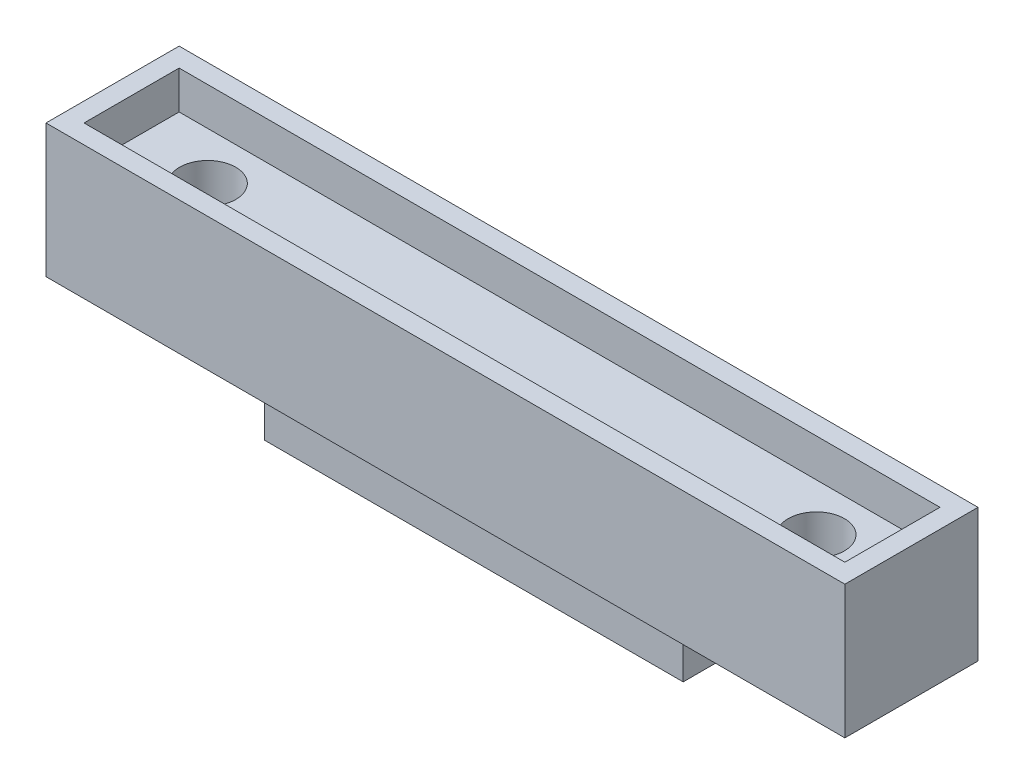
SolidWorks part; units mm, degrees
ref_plane "Front Plane" through (0, 0, 0) normal (0, 0, 1) x (1, 0, 0)
ref_plane "Top Plane" through (0, 0, 0) normal (0, 1, 0) x (1, 0, 0)
ref_plane "Right Plane" through (0, 0, 0) normal (1, 0, 0) x (0, 0, -1)
sketch "Sketch1" plane through (0, 0, 0) normal (0, 1, 0) x (1, 0, 0)
  line L1 (0, 7) -> (42, 7)
  line L2 (0, 7) -> (0, 0)
  line L3 (0, 0) -> (42, 0)
  line L4 (42, 7) -> (42, 0)
  dimension "D1" = 7
  dimension "D2" = 42
extrude "Riser" add sketch "Sketch1" along normal blind 7
sketch "Sketch2" plane through (0, 0, 0) normal (0, -1, 0) x (1, 0, 0)
  line L0 (0, -7) -> (0, 0) construction
  line L1 (21, 0) -> (21, -7) construction
  line L2 (0, 0) -> (42, 0) construction
  line L3 (42, -7) -> (0, -7) construction
  circle A0 centre (5, -3.5) radius 1.475
  circle A1 centre (37, -3.5) radius 1.475
  point P6 (0, -3.5)
  dimension "D2" = 2.95
  dimension "D1" = 5
extrude "Mounting Holes" cut sketch "Sketch2" against normal through all
sketch "Sketch3" plane through (0, 7, 0) normal (0, 1, 0) x (1, 0, 0)
  line L0 (41, 6) -> (1, 6)
  line L1 (1, 6) -> (1, 1)
  line L2 (1, 1) -> (41, 1)
  line L3 (41, 1) -> (41, 6)
  line L4 (0, 7) -> (0, 0)
  line L5 (0, 0) -> (42, 0)
  line L6 (42, 0) -> (42, 7)
  line L7 (42, 7) -> (0, 7)
  line L8 (0, 7) -> (0, 0)
  line L9 (0, 0) -> (42, 0)
  line L10 (42, 0) -> (42, 7)
  line L11 (42, 7) -> (0, 7)
  dimension "D1" = 0
  dimension "D2" = 1
extrude "Recess (4-Sides)" cut sketch "Sketch3" against normal blind 2 contours L0 L1 L2 L3
sketch "Sketch4" plane through (0, 7, 0) normal (0, 1, 0) x (1, 0, 0)
  line L0 (0, 0) -> (42, 0) construction
  line L1 (1, 6) -> (41, 6)
  line L2 (1, 6) -> (1, 0)
  line L3 (1, 0) -> (41, 0)
  line L4 (41, 6) -> (41, 0)
  line L5 (0, 7) -> (0, 0) construction
  line L6 (42, 0) -> (42, 7) construction
  line L7 (42, 7) -> (0, 7) construction
  dimension "D1" = 1
  dimension "D2" = 1
  dimension "D3" = 1
extrude "Recess (3-Sides)" [suppressed] cut sketch "Sketch4" against normal blind 2
sketch "Sketch5" plane through (0, 0, 0) normal (0, -1, 0) x (1, 0, 0)
  line L1 (10, -1.5) -> (32, -1.5)
  line L2 (10, -1.5) -> (10, -5.5)
  line L3 (10, -5.5) -> (32, -5.5)
  line L4 (32, -1.5) -> (32, -5.5)
  point P4 (37, -3.5)
  point P5 (5, -3.5)
  point P6 (10, -3.5)
  point P9 (32, -3.5)
  dimension "D1" = 5
  dimension "D2" = 5
  dimension "D3" = 4
extrude "Alignment Tab" add sketch "Sketch5" along normal blind 3.2
